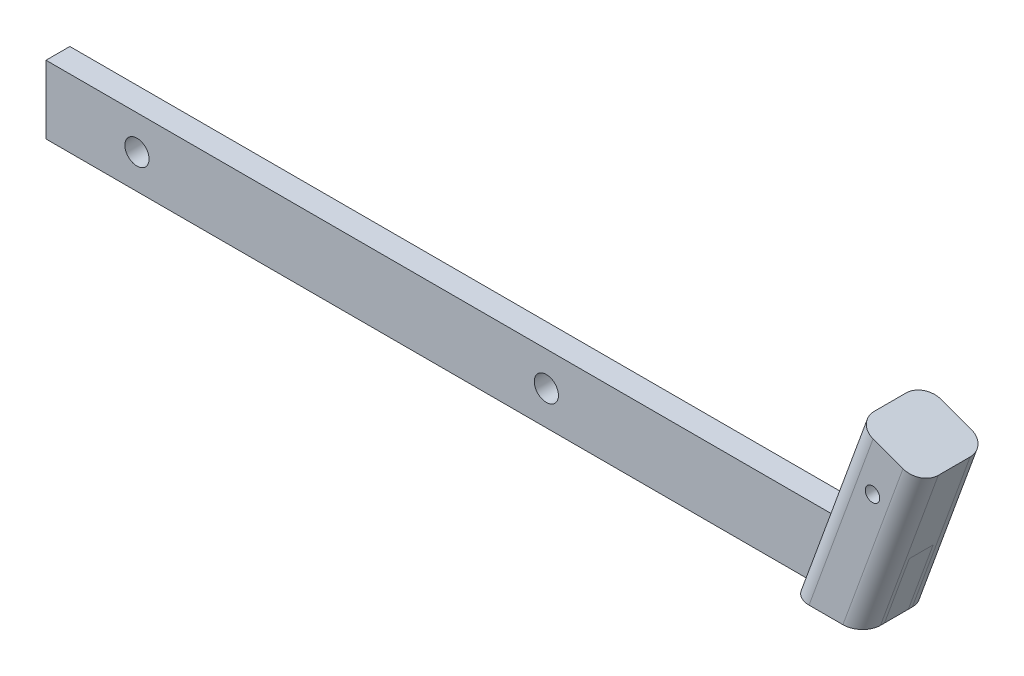
SolidWorks part; units mm, degrees
other "DetailItem2"
other "Weld Folder"
material "AISI 304"
ref_plane "Front Plane" through (0, 0, 0) normal (0, 0, 1) x (1, 0, 0)
ref_plane "Top Plane" through (0, 0, 0) normal (0, 1, 0) x (1, 0, 0)
ref_plane "Right Plane" through (0, 0, 0) normal (1, 0, 0) x (0, 0, -1)
sketch "Sketch8" plane through (0, 0, 0) normal (0, 0, 1) x (1, 0, 0)
  line L0 (0, 0) -> (-223.9659, 0)
  line L1 (0, 0) -> (17.3341, 47.625)
  dimension "D1" = 70
  dimension "D2" = 47.625
  dimension "D3" = 241.3
ref_plane "Plane1" through (17.3341, 47.625, 0) normal (0.342, 0.9397, 0) x (0.9397, -0.342, 0)
sketch "Sketch9" plane through (17.3341, 47.625, 0) normal (0.342, 0.9397, 0) x (0.9397, -0.342, 0)
  line L1 (9.525, 9.525) -> (-9.525, 9.525)
  line L2 (9.525, 9.525) -> (9.525, -9.525)
  line L3 (9.525, -9.525) -> (-9.525, -9.525)
  line L4 (-9.525, 9.525) -> (-9.525, -9.525)
  line L5 (9.525, 9.525) -> (-9.525, -9.525) construction
  line L6 (9.525, -9.525) -> (-9.525, 9.525) construction
  point P0 (0, 0)
  dimension "D1" = 19.05
extrude "Boss-Extrude2" add sketch "Sketch9" against normal up to surface (47.2146 mm away) up to plane "Top Plane"
ref_plane "Plane2" through (-223.9659, 0, 0) normal (-1, 0, 0) x (0, 0, 1)
sketch "Sketch11" plane through (-223.9659, 0, 0) normal (-1, 0, 0) x (0, 0, 1)
  line L0 (0, 19.05) -> (0, 0) construction
  line L1 (-3.3274, 0) -> (3.3274, 0)
  line L2 (-3.3274, 0) -> (-3.3274, 19.05)
  line L3 (-3.3274, 19.05) -> (3.3274, 19.05)
  line L4 (3.3274, 0) -> (3.3274, 19.05)
  point P10 (0, 0)
  dimension "D1" = 6.6548
  dimension "D2" = 19.05
hole_wizard "#10-32 Tapped Hole1" positions "Sketch12" profile "Sketch13" tap size "#10-32" standard "ANSI Inch" end condition through all
sketch "Sketch12" plane through (0, 0, -9.525) normal (0, 0, -1) x (-1, 0, 0)
  line L0 (-17.3341, 47.625) -> (-12.9904, 35.6909) construction
  line L1 (-26.2847, 44.3673) -> (-8.3835, 50.8827) construction
  point P0 (-12.9904, 35.6909)
  dimension "D1" = 12.7
cosmetic thread "Hole Thread1" parameters "D2"=4.826
sketch "Sketch13" plane through (12.9904, 35.6909, -9.525) normal (1, 0, 0) x (0, 1, 0)
  line L0 (0, 0) -> (0, 19.05)
  line L1 (0, 19.05) -> (2.0193, 19.05)
  line L2 (2.0193, 19.05) -> (2.0193, 0)
  line L5 (2.0193, 0) -> (0, 0)
  line L11 (0, -6.35) -> (0, 107.95) construction
  dimension "Thru Tap Drill Dia." = 4.0386
  dimension "Thru Tap Drill Depth" = 19.05
extrude "Cut-Extrude2" cut sketch "Sketch11" against normal up to surface (234.1022 mm away) up to face at (18.2105, 22.1836, 0)
fillet "Fillet1" radius 5.08 4 edges at (18.2105, 22.1836, 9.525) (-0.8764, 25.4414, 9.525) (-0.8764, 25.4414, -9.525) (18.2105, 22.1836, -9.525)
extrude "Boss-Extrude3" add sketch "Sketch11<2>" against normal up to surface (234.1022 mm away) separate body up to face at (15.9068, 15.8543, 0)
sketch "Sketch11<2>" plane through (-223.9659, 0, 0) normal (-1, 0, 0) x (0, 0, 1) same geometry as "Sketch11"
other "Fillet Bead1" [suppressed] parameters "D10"=6.35, "D11"=3.175, "D12"=0, "D13"=3.175, "D14"=0
hole_wizard "1/4 Clearance Hole1" positions "Sketch16" profile "Sketch17" hole size "1/4" standard "ANSI Inch" end condition through all
sketch "Sketch16" plane through (0, 0, -3.3274) normal (0, 0, -1) x (-1, 0, 0)
  line L0 (223.9659, 9.525) -> (0, 9.525) construction
  line L2 (223.9659, 19.05) -> (223.9659, 0) construction
  point P8 (198.5659, 9.525)
  point P10 (84.2659, 9.525)
  point P18 (223.9659, 9.525)
  dimension "D1" = 114.3
  dimension "D2" = 25.4
sketch "Sketch17" plane through (-84.2659, 9.525, -3.3274) normal (1, 0, 0) x (0, 1, 0)
  line L0 (0, 0) -> (0, 12.8524)
  line L1 (0, 12.8524) -> (3.3782, 12.8524)
  line L2 (3.3782, 12.8524) -> (3.3782, 0)
  line L5 (3.3782, 0) -> (0, 0)
  line L11 (0, -6.35) -> (0, 107.95) construction
  dimension "Thru Hole Dia." = 6.7564
  dimension "Thru Hole Depth" = 12.8524
